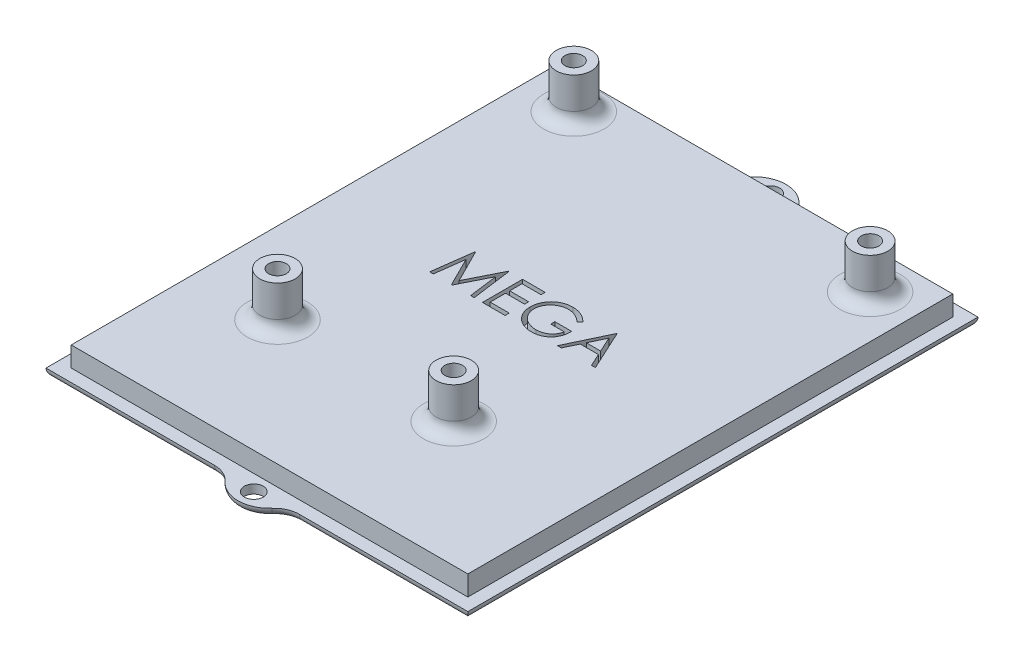
SolidWorks part; units mm, degrees
ref_plane "Front Plane" through (0, 0, 0) normal (0, 0, 1) x (1, 0, 0)
ref_plane "Top Plane" through (0, 0, 0) normal (0, 1, 0) x (1, 0, 0)
ref_plane "Right Plane" through (0, 0, 0) normal (1, 0, 0) x (0, 0, -1)
sketch "Sketch1" plane through (0, 0, 0) normal (0, 1, 0) x (1, 0, 0)
  line L0 (-31.45, 38.45) -> (31.45, 38.45)
  line L5 (-31.45, 38.45) -> (-31.45, -38.45)
  line L6 (-31.45, -38.45) -> (31.45, -38.45)
  line L7 (31.45, 38.45) -> (31.45, -38.45)
  point P11 (-31.45, 0)
  point P12 (0, -38.45)
  dimension "D3" = 76.9
  dimension "D4" = 62.9
extrude "Boss-Extrude1" add sketch "Sketch1" along normal blind 4.575
sketch "Sketch2" plane through (0, 4.575, 0) normal (0, 1, 0) x (1, 0, 0)
  line L0 (9.37, -18.62) -> (9.37, 32.18) construction
  line L1 (24.61, 32.18) -> (9.37, 32.18) construction
  line L2 (9.37, -18.62) -> (-18.57, -18.62) construction
  line L3 (-18.57, -18.62) -> (-18.57, 33.45) construction
  line L4 (0, -38.45) -> (0, 38.45) construction
  line L5 (-31.45, 0) -> (31.45, 0) construction
  line L6 (-18.57, 33.45) -> (-23.65, 33.45) construction
  line L11 (-31.45, 38.45) -> (-31.45, -38.45) construction
  line L12 (-31.45, -38.45) -> (31.45, -38.45) construction
  line L13 (31.45, 38.45) -> (-31.45, 38.45) construction
  line L14 (31.45, -38.45) -> (31.45, 38.45) construction
  circle A0 centre (9.37, -18.62) radius 2.8
  circle A1 centre (24.61, 32.18) radius 2.8
  circle A2 centre (-23.65, 33.45) radius 2.8
  circle A3 centre (-18.57, -18.62) radius 2.8
  circle A4 centre (24.61, 32.18) radius 1.4
  circle A5 centre (9.37, -18.62) radius 1.4
  circle A6 centre (-18.57, -18.62) radius 1.4
  circle A7 centre (-23.65, 33.45) radius 1.4
  dimension "D7" = 2.8
  dimension "D10" = 1.4
  dimension "D6" = 7.8
  dimension "D8" = 5
  dimension "D1" = 27.94
  dimension "D2" = 15.24
  dimension "D3" = 5.08
  dimension "D4" = 1.27
  dimension "D5" = 50.8
extrude "Boss-Extrude2" add sketch "Sketch2" along normal blind 7
sketch "Sketch3" plane through (0, 4.575, 0) normal (0, 1, 0) x (1, 0, 0)
  circle A0 centre (9.37, -18.62) radius 1.4
  circle A1 centre (-18.57, -18.62) radius 1.4
  circle A2 centre (-23.65, 33.45) radius 1.4
  circle A3 centre (24.61, 32.18) radius 1.4
  circle A4 centre (24.61, 32.18) radius 1.4 construction
  circle A5 centre (-23.65, 33.45) radius 1.4 construction
extrude "Cut-Extrude1" cut sketch "Sketch3" against normal offset from surface (3.575 mm away) 1 up to face at (0, 0, 0)
sketch "Sketch7" plane through (0, 0, 0) normal (0, -1, 0) x (1, 0, 0)
  line L8 (-33.45, 40.45) -> (-33.45, -40.45)
  line L9 (-33.45, -40.45) -> (33.45, -40.45)
  line L10 (33.45, -40.45) -> (33.45, 40.45)
  line L11 (33.45, 40.45) -> (-33.45, 40.45)
  line L12 (-33.45, 40.45) -> (-33.45, -40.45)
  line L13 (-33.45, -40.45) -> (33.45, -40.45)
  line L14 (33.45, -40.45) -> (33.45, 40.45)
  line L15 (33.45, 40.45) -> (-33.45, 40.45)
  dimension "D1" = 2
extrude "Boss-Extrude5" add sketch "Sketch7" against normal blind 1.4
sketch "Sketch4" plane through (0, 0, 0) normal (0, 1, 0) x (1, 0, 0)
  line L2 (-6.7082, -40.45) -> (6.7082, -40.45)
  line L3 (-31.45, -38.45) -> (31.45, -38.45) construction
  line L6 (-31.45, -38.45) -> (31.45, -38.45) construction
  line L7 (33.45, -40.45) -> (-33.45, -40.45) construction
  arc A3 (-6.7082, -40.45) -> (-3.7268, -41.7833) centre (-6.7082, -44.45) cw
  arc A4 (-3.7268, -41.7833) -> (3.7268, -41.7833) centre (0, -38.45) ccw
  arc A5 (3.7268, -41.7833) -> (6.7082, -40.45) centre (6.7082, -44.45) cw
  point P6 (0, -38.45)
  dimension "D1" = 5
  dimension "D2" = 4
extrude "Boss-Extrude3" add sketch "Sketch4" along normal blind 1.4
sketch "Sketch8" plane through (0, 1.4, 0) normal (0, 1, 0) x (1, 0, 0)
  line L0 (0, -38.45) -> (0, -43.45) construction
  line L1 (31.45, -38.45) -> (-31.45, -38.45) construction
  arc A0 (-3.7268, -41.7833) -> (3.7268, -41.7833) centre (0, -38.45) ccw construction
  circle A1 centre (0, -40.95) radius 1.5
  dimension "D1" = 3
extrude "Cut-Extrude3" cut sketch "Sketch8" against normal up to next
mirror "Mirror1" about plane through (0, 0, 0) normal (0, 0, 1) of "Cut-Extrude3", "Boss-Extrude3"
sketch "Sketch5" plane through (0, 4.575, 0) normal (0, 1, 0) x (1, 0, 0)
  line L0 (-15, 0) -> (15, 0) construction
  text T0 "MEGA" font "Century Gothic" height in points 24
  point P6 (0, 0)
  dimension "D1" = 30
extrude "Cut-Extrude2" cut sketch "Sketch5" against normal blind 2
fillet "Fillet1" radius 1.4 12 edges at (20.0791, 0, -40.45) (5.0752, 0, -40.7985) (0, 0, -43.45) (-5.0752, 0, -40.7985) (-20.0791, 0, -40.45) (-33.45, 0, 0) (-20.0791, 0, 40.45) (-5.0752, 0, 40.7985) (0, 0, 43.45) (5.0752, 0, 40.7985) (20.0791, 0, 40.45) (33.45, 0, 0)
fillet "Fillet2" radius 2 4 edges at (24.61, 4.575, -29.38) (-23.65, 4.575, -30.65) (9.37, 4.575, 21.42) (-18.57, 4.575, 21.42)
